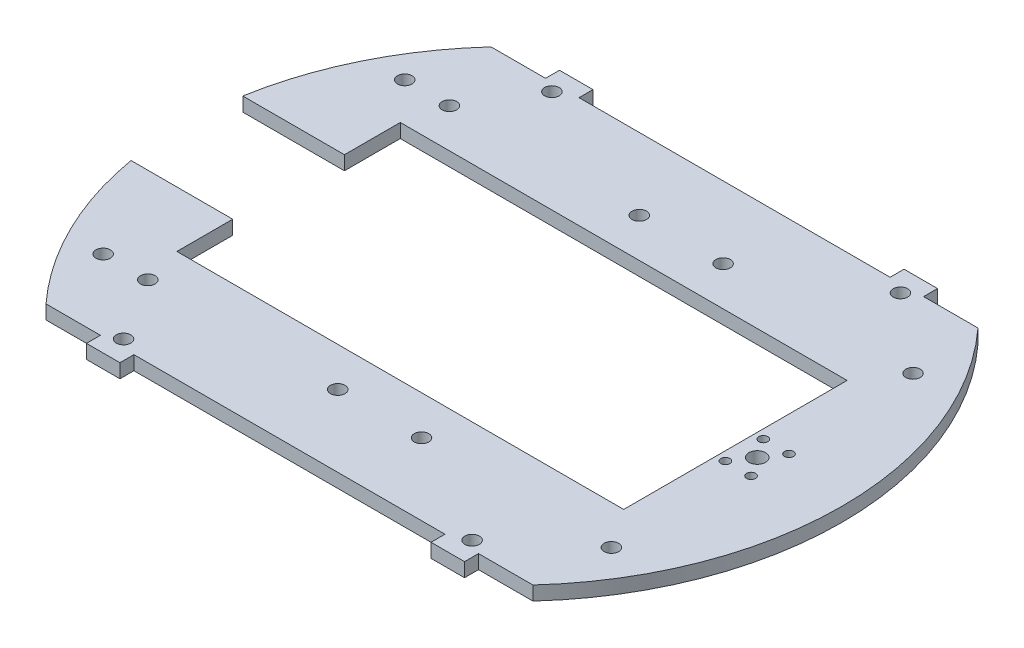
SolidWorks part; units mm, degrees
material "Acrylic (Medium-high impact)"
ref_plane "Front Plane" through (0, 0, 0) normal (0, 0, 1) x (1, 0, 0)
ref_plane "Top Plane" through (0, 0, 0) normal (0, 1, 0) x (1, 0, 0)
ref_plane "Right Plane" through (0, 0, 0) normal (1, 0, 0) x (0, 0, -1)
sketch "Sketch1" plane through (0, 0, 0) normal (0, 1, 0) x (1, 0, 0)
  line L0 (-73.9169, 12.7) -> (-73.9169, -12.7)
  line L1 (-35.3642, -50.6035) -> (-35.3642, -53.7785)
  line L2 (-55.356, -50.6035) -> (-42.9842, -50.6035)
  line L3 (-55.356, 50.6035) -> (-42.9842, 50.6035)
  line L4 (-48.5169, -34.29) -> (-48.5169, 34.29) construction
  line L5 (-48.5169, 34.29) -> (-5.3369, 34.29) construction
  line L6 (-5.3369, 34.29) -> (-5.3369, -34.29) construction
  line L7 (-5.3369, -34.29) -> (-48.5169, -34.29) construction
  line L8 (-73.9169, 0) -> (-48.5169, 0) construction
  line L9 (0, 50.6035) -> (0, -51.6195) construction
  line L10 (-73.9169, 12.7) -> (-73.9169, -12.7) construction
  line L11 (-50.8, 25.4) -> (50.8, 25.4)
  line L12 (-50.8, 25.4) -> (-50.8, -25.4)
  line L13 (-50.8, -25.4) -> (50.8, -25.4)
  line L14 (50.8, 25.4) -> (50.8, -25.4)
  line L15 (0, 0) -> (0, 25.4) construction
  line L16 (0, 0) -> (-50.8, 0) construction
  line L17 (13.7131, 34.29) -> (13.7131, -34.29) construction
  line L18 (13.7131, -34.29) -> (56.8931, -34.29) construction
  line L19 (56.8931, -34.29) -> (56.8931, 34.29) construction
  line L20 (56.8931, 34.29) -> (13.7131, 34.29) construction
  line L21 (39.6269, 48.6985) -> (39.6269, 50.6035) construction
  line L22 (39.6269, -48.6985) -> (39.6269, -50.6035) construction
  line L23 (-39.6269, -48.6985) -> (-39.6269, -50.6035) construction
  line L24 (-39.6269, 48.6985) -> (-39.6269, 50.6035) construction
  line L25 (39.6269, 48.6985) -> (41.2779, 48.6985) construction
  line L26 (39.6269, -48.6985) -> (41.2779, -48.6985) construction
  line L27 (-35.3642, -50.6035) -> (35.3642, -50.6035)
  line L28 (35.3642, -50.6035) -> (35.3642, -53.7785)
  line L29 (35.3642, -53.7785) -> (42.9842, -53.7785)
  line L30 (42.9842, -50.6035) -> (42.9842, -53.7785)
  line L31 (-35.3642, -53.7785) -> (-42.9842, -53.7785)
  line L32 (-42.9842, -50.6035) -> (-42.9842, -53.7785)
  line L33 (42.9842, 50.6035) -> (42.9842, 53.7785)
  line L34 (35.3642, 53.7785) -> (42.9842, 53.7785)
  line L35 (35.3642, 50.6035) -> (35.3642, 53.7785)
  line L36 (-35.3642, 50.6035) -> (-35.3642, 53.7785)
  line L37 (-35.3642, 53.7785) -> (-42.9842, 53.7785)
  line L38 (-42.9842, 50.6035) -> (-42.9842, 53.7785)
  line L39 (42.9842, -50.6035) -> (55.356, -50.6035)
  line L40 (42.9842, 50.6035) -> (55.356, 50.6035)
  line L41 (-35.3642, 50.6035) -> (35.3642, 50.6035)
  line L42 (50.8, 6.35) -> (60.7031, 6.35) construction
  line L43 (60.7031, -38.1) -> (60.7031, 38.1) construction
  line L44 (60.7031, 6.35) -> (60.7031, -6.35) construction
  line L45 (60.7031, -6.35) -> (50.8, -6.35) construction
  line L46 (60.7031, 0) -> (50.8, 0) construction
  line L47 (58.6711, 4.318) -> (58.6711, -4.318) construction
  line L48 (58.6711, -4.318) -> (52.832, -4.318) construction
  line L49 (52.832, -4.318) -> (52.832, 4.318) construction
  line L50 (52.832, 4.318) -> (58.6711, 4.318) construction
  line L51 (58.6711, 4.318) -> (58.6711, 6.35) construction
  line L52 (58.6711, 4.318) -> (60.7031, 4.318) construction
  line L53 (52.832, 4.318) -> (52.832, 6.35) construction
  line L54 (52.832, 4.318) -> (50.8, 4.318) construction
  line L55 (52.832, -4.318) -> (52.832, -6.35) construction
  line L56 (52.832, -4.318) -> (50.8, -4.318) construction
  line L57 (58.6711, -4.318) -> (58.6711, -6.35) construction
  line L58 (58.6711, -4.318) -> (60.7031, -4.318) construction
  arc A0 (-73.9169, -12.7) -> (-55.356, -50.6035) centre (0, 0) ccw
  circle A1 centre (13.7131, 34.29) radius 1.651
  arc A2 (-55.356, 50.6035) -> (-73.9169, 12.7) centre (0, 0) ccw
  arc A3 (55.356, -50.6035) -> (55.356, 50.6035) centre (0, 0) ccw
  circle A4 centre (-58.6769, -34.29) radius 1.651
  circle A5 centre (-58.6769, 34.29) radius 1.651
  circle A6 centre (-39.6269, 48.6985) radius 1.651
  circle A7 centre (39.6269, 48.6985) radius 1.651
  circle A8 centre (-39.6269, -48.6985) radius 1.651
  circle A9 centre (39.6269, -48.6985) radius 1.651
  circle A10 centre (56.8931, 34.29) radius 1.651
  circle A11 centre (-58.6769, 34.29) radius 1.651 construction
  circle A12 centre (-48.5169, 34.29) radius 1.651
  circle A13 centre (-5.3369, 34.29) radius 1.651
  circle A14 centre (-5.3369, -34.29) radius 1.651
  circle A15 centre (-48.5169, -34.29) radius 1.651
  circle A16 centre (13.7131, -34.29) radius 1.651
  circle A17 centre (56.8931, -34.29) radius 1.651
  circle A18 centre (55.7515, 0) radius 1.905
  circle A19 centre (58.6711, 4.318) radius 1.016
  circle A20 centre (58.6711, -4.318) radius 1.016
  circle A21 centre (52.832, -4.318) radius 1.016
  circle A22 centre (52.832, 4.318) radius 1.016
  dimension "D3" = 3.302
  dimension "D8" = 3.81
  dimension "D11" = 2.032
  dimension "D1" = 43.18
  dimension "D2" = 68.58
  dimension "D4" = 25.4
  dimension "D5" = 101.6
  dimension "D6" = 50.8
  dimension "D7" = 19.05
  dimension "D9" = 12.7
  dimension "D10" = 19.05
  dimension "D12" = 2.032
extrude "Boss-Extrude1" add sketch "Sketch1" along normal blind 3.175
sketch "Sketch3" plane through (0, 3.175, 0) normal (0, 1, 0) x (1, 0, 0)
  line L0 (-50.8, 25.4) -> (-50.8, -25.4) construction
  line L1 (-73.9169, 12.7) -> (-50.8, 12.7)
  line L2 (-73.9169, 12.7) -> (-73.9169, -12.7)
  line L3 (-73.9169, -12.7) -> (-50.8, -12.7)
  line L4 (-50.8, 12.7) -> (-50.8, -12.7)
extrude "Cut-Extrude2" cut sketch "Sketch3" against normal up to surface (3.175 mm away) up to face at (52.832, 0, 5.334)
